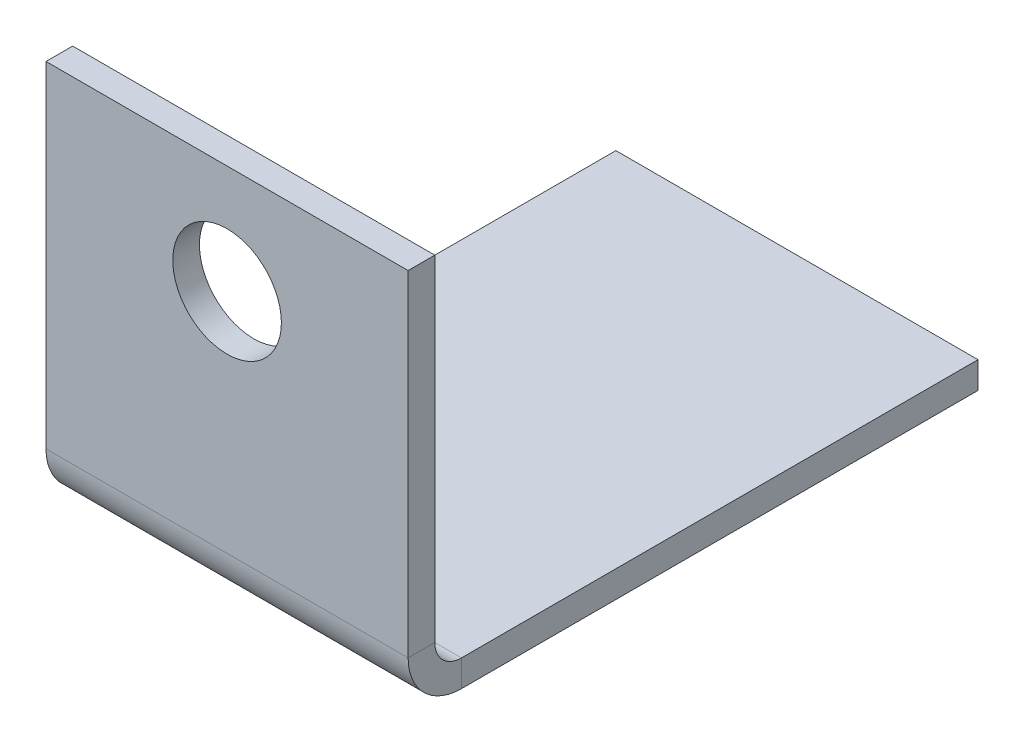
SolidWorks part; units mm, degrees
note: The reader was unsure of these and kept them because the rebuilt part matched: flange length of "Brida de arista1".
ref_plane "Alzado" through (0, 0, 0) normal (0, 0, 1) x (1, 0, 0)
ref_plane "Planta" through (0, 0, 0) normal (0, 1, 0) x (1, 0, 0)
ref_plane "Vista lateral" through (0, 0, 0) normal (1, 0, 0) x (0, 0, -1)
sketch "Croquis1" plane through (0, 0, 0) normal (0, 1, 0) x (1, 0, 0)
  line L1 (-5, -7.5) -> (5, -7.5)
  line L2 (-5, -7.5) -> (-5, 7.5)
  line L3 (-5, 7.5) -> (5, 7.5)
  line L4 (5, -7.5) -> (5, 7.5)
  line L5 (-5, -7.5) -> (5, 7.5) construction
  line L6 (-5, 7.5) -> (5, -7.5) construction
  point P0 (0, 0)
  dimension "D1" = 10
  dimension "D2" = 15
sheet metal parameters "Chapa metálica1" thickness 0.7366 parameters "D1"=0.7366
base flange "Brida base1" sketch "Croquis1" thickness 0.7366 reverse thickness direction no parameters "D1"=0.7366
edge flange "Brida de arista1" sketch "Croquis6" flange angle 90 flange length 10 flange position material outside bend radius 0.7366 thickness 0.7366 relief rectangular parameters "D6"=10
sketch "Croquis6" plane through (0, 0, 7.5) normal (0, 0, 1) x (1, 0, 0)
  line L0 (-5, 0) -> (5, 0) construction
  line L1 (-5, 0) -> (5, 0)
  line L2 (-5, 0) -> (-5, 10)
  line L3 (-5, 10) -> (5, 10)
  line L4 (5, 10) -> (5, 0)
bend "Pliegue de arista1" bend radius 0.7366 bend angle 90 parameters "D5"=1
sketch "Croquis7" plane through (0, 0, 8.2366) normal (0, 0, 1) x (1, 0, 0)
  line L0 (5, 10) -> (-5, 10) construction
  line L1 (0, 10) -> (0, 7) construction
  circle A0 centre (0, 7) radius 1.5
  dimension "D1" = 3
  dimension "D2" = 3
extrude "Cortar-Extruir1" cut sketch "Croquis7" against normal blind 10 normal cut yes
flat pattern "Chapa desplegada1" [suppressed]
sketch "Líneas de pliegue1" plane through (0, 0, 0) normal (0, 1, 0) x (1, 0, 0)
sketch3d "Cuadro delimitador1" [suppressed]
  line L0 (5, -7.5, 0) -> (5, 7.5, 0) construction
  line L1 (-5, -7.5, 0) -> (-5, 7.5, 0) construction
  line L2 (5, -7.5, 0) -> (-5, -7.5, 0) construction
  line L3 (5, 7.5, 0) -> (-5, 7.5, 0) construction
bend of the flat pattern "Aplanar-<Pliegue de arista1>1"
